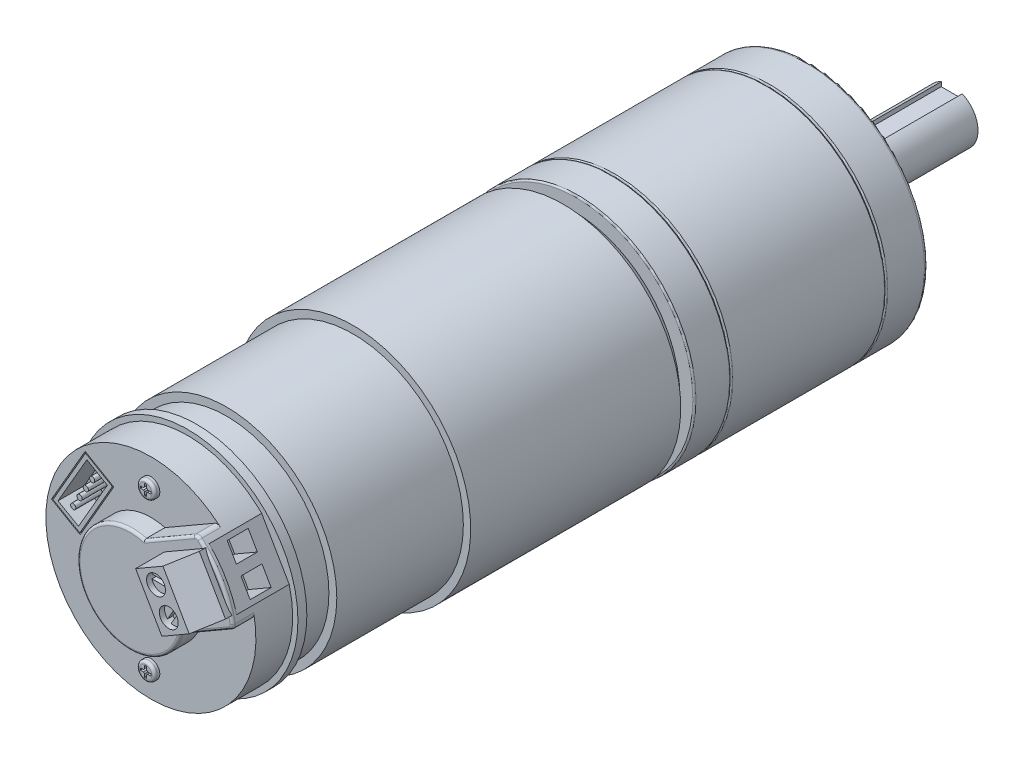
SolidWorks part; units mm, degrees
ref_plane "Front Plane" through (0, 0, 0) normal (0, 0, 1) x (1, 0, 0)
ref_plane "Top Plane" through (0, 0, 0) normal (0, 1, 0) x (1, 0, 0)
ref_plane "Right Plane" through (0, 0, 0) normal (1, 0, 0) x (0, 0, -1)
sketch "Sketch1" plane through (0, 0, 0) normal (0, 0, 1) x (1, 0, 0)
  circle A0 centre (-32.232, 14.9868) radius 22.5
extrude "Boss-Extrude1" add sketch "Sketch1" along normal blind 8
fillet "Fillet1" radius 0.3 1 edges at (-9.732, 14.9868, 8)
sketch "Sketch2" plane through (0, 0, 8) normal (0, 0, 1) x (1, 0, 0)
  circle A0 centre (-32.232, 14.9868) radius 22.5
extrude "Boss-Extrude2" add sketch "Sketch2" along normal blind 29.5
fillet "Fillet3" radius 0.3 1 edges at (-9.732, 14.9868, 37.5)
sketch "Sketch3" plane through (0, 0, 37.5) normal (0, 0, 1) x (1, 0, 0)
  circle A0 centre (-32.232, 14.9868) radius 22.5
extrude "Boss-Extrude5" add sketch "Sketch3" along normal blind 7
fillet "Fillet4" radius 0.3 3 edges at (-9.732, 14.9868, 8) (-9.732, 14.9868, 37.5) (-9.732, 14.9868, 44.5)
sketch "Sketch4" plane through (0, 0, 44.5) normal (0, 0, 1) x (1, 0, 0)
  circle A0 centre (-32.232, 14.9868) radius 5
extrude "Boss-Extrude7" add sketch "Sketch4" along normal blind 0.1
sketch "Sketch5" plane through (0, 0, 44.6) normal (0, 0, 1) x (1, 0, 0)
  circle A0 centre (-32.232, 14.9868) radius 21
extrude "Boss-Extrude8" add sketch "Sketch5" along normal blind 66.5
fillet "Fillet6" radius 2 1 edges at (-11.232, 14.9868, 44.6)
ref_plane "Plane1" through (0, 0, 47) normal (0, 0, 1) x (1, 0, 0)
sketch "Sketch6" plane through (0, 0, 47) normal (0, 0, 1) x (1, 0, 0)
  line L2 (-28.132, -5.609) -> (-28.132, -7.0347)
  line L4 (-36.332, -5.609) -> (-36.332, -7.0347)
  arc A0 (-28.132, -7.0347) -> (-36.332, -7.0347) centre (-32.232, 14.9868) ccw
  arc A1 (-28.132, -5.609) -> (-36.332, -5.609) centre (-32.232, 14.9868) ccw
  point P4 (-32.232, -6.0132)
extrude "Boss-Extrude9" add sketch "Sketch6" along normal blind 40
sketch "Sketch7" plane through (0, 0, 111.1) normal (0, 0, 1) x (1, 0, 0)
  circle A0 centre (-32.232, 14.9868) radius 19.5
extrude "Boss-Extrude10" add sketch "Sketch7" along normal blind 5.7
sketch "Sketch8" plane through (0, 0, 116.8) normal (0, 0, 1) x (1, 0, 0)
  circle A0 centre (-32.232, 14.9868) radius 21
extrude "Boss-Extrude11" add sketch "Sketch8" along normal blind 1.7
sketch "Sketch9" plane through (0, 0, 118.5) normal (0, 0, 1) x (1, 0, 0)
  circle A0 centre (-32.232, 14.9868) radius 20
extrude "Boss-Extrude12" add sketch "Sketch9" along normal blind 7
fillet "Fillet7" radius 0.7 1 edges at (-9.732, 14.9868, 0)
sketch "Sketch21" plane through (0, 0, 125.5) normal (0, 0, 1) x (1, 0, 0)
  line L0 (-45.6944, 15.3693) -> (-51.1503, 18.5193)
  line L2 (-39.2944, 26.4544) -> (-44.7503, 29.6044)
  line L3 (-44.7503, 29.6044) -> (-51.1503, 18.5193)
  line L4 (-39.2944, 26.4544) -> (-45.6944, 15.3693)
  point P6 (-42.4944, 20.9118)
extrude "Cut-Extrude5" cut sketch "Sketch21" against normal blind 5
sketch "Sketch22" plane through (0, 0, 120.5) normal (0, 0, 1) x (1, 0, 0)
  line L0 (-44.4209, 28.375) -> (-49.9209, 18.8487)
  line L1 (-49.9209, 18.8487) -> (-46.0238, 16.5987)
  line L2 (-46.0238, 16.5987) -> (-40.5238, 26.125)
  line L3 (-40.5238, 26.125) -> (-44.4209, 28.375)
  line L4 (-39.5676, 26.3812) -> (-44.6771, 29.3312)
  line L5 (-44.6771, 29.3312) -> (-50.8771, 18.5925)
  line L6 (-50.8771, 18.5925) -> (-45.7676, 15.6425)
  line L7 (-45.7676, 15.6425) -> (-39.5676, 26.3812)
  circle A0 centre (-45.8223, 21.4476) radius 0.5
  circle A1 centre (-47.0223, 19.3691) radius 0.5
  circle A2 centre (-43.4223, 25.6045) radius 0.5
  circle A3 centre (-44.6223, 23.5261) radius 0.5
extrude "Boss-Extrude20" add sketch "Sketch22" along normal blind 5 contours L6 L7 L4 L5 L3 L2 L1 L0 | A2 | A3 | A0 | A1 region at (-42.8213, 21.1006, 120.5) region at (-45.8223, 21.4476, 120.5) region at (-47.0223, 19.3691, 120.5) region at (-43.4223, 25.6045, 120.5) region at (-44.6223, 23.5261, 120.5)
sketch "Sketch23" plane through (0, 0, 125.5) normal (0, 0, 1) x (1, 0, 0)
  line L1 (-29.5473, 24.6197) -> (-20.1195, 30.0629)
  line L2 (-22.5473, 12.4954) -> (-13.1195, 17.9385)
  arc A0 (-29.5473, 24.6197) -> (-22.5473, 12.4954) centre (-32.232, 14.9868) ccw
  arc A1 (-13.1195, 17.9385) -> (-12.6399, 19.0055) centre (-13.6195, 18.8046) ccw
  arc A2 (-20.1195, 30.0629) -> (-18.9557, 29.9448) centre (-19.6195, 29.1969) cw
  arc A4 (-12.6399, 19.0055) -> (-18.9557, 29.9448) centre (-32.232, 14.9868) ccw
  point P10 (-42.4944, 20.9118)
  point P11 (-24.8334, 27.3413)
  dimension "D1" = 1
extrude "Boss-Extrude21" add sketch "Sketch23" along normal blind 4
sketch "Sketch24" plane through (0, 0, 129.5) normal (0, 0, 1) x (1, 0, 0)
  line L1 (-13.0177, 20.3067) -> (-20.6387, 15.9067)
  line L2 (-18.0177, 28.967) -> (-25.6387, 24.567)
  line L3 (-25.6387, 24.567) -> (-20.6387, 15.9067)
  line L4 (-18.0177, 28.967) -> (-13.0177, 20.3067)
  point P6 (-15.5177, 24.6368)
  point P7 (-23.1387, 20.2368)
extrude "Boss-Extrude22" add sketch "Sketch24" along normal blind 5.5
sketch "Sketch25" plane through (-12.0475, 20.8669, 0) normal (0.5, -0.866, 0) x (0.866, 0.5, 0)
  line L0 (-1.1203, 130.5) -> (-3.9203, 135)
  line L1 (-3.9203, 135) -> (-1.1203, 135)
  line L2 (-1.1203, 135) -> (-1.1203, 130.5)
extrude "Cut-Extrude6" cut sketch "Sketch25" against normal through all
sketch "Sketch26" plane through (0, 0, 125.5) normal (0, 0, 1) x (1, 0, 0)
  line L0 (-31.832, 29.7868) -> (-31.232, 29.7868)
  line L1 (-33.232, 29.7868) -> (-33.232, 30.1868)
  line L2 (-31.832, 30.1868) -> (-31.232, 30.1868)
  line L3 (-32.032, 30.3868) -> (-32.032, 30.9868)
  line L4 (-32.432, 30.3868) -> (-32.432, 30.9868)
  line L5 (-32.632, 30.1868) -> (-33.232, 30.1868)
  line L6 (-32.432, 30.9868) -> (-32.032, 30.9868)
  line L7 (-32.032, 29.5868) -> (-32.032, 28.9868)
  line L8 (-32.432, 29.5868) -> (-32.432, 28.9868)
  line L9 (-32.632, 29.7868) -> (-33.232, 29.7868)
  line L10 (-31.232, 30.1868) -> (-31.232, 29.7868)
  line L11 (-32.432, 28.9868) -> (-32.032, 28.9868)
  line L12 (-32.632, 29.7868) -> (-32.432, 29.5868)
  line L13 (-32.432, 30.3868) -> (-32.632, 30.1868)
  line L14 (-32.032, 30.3868) -> (-31.832, 30.1868)
  line L15 (-31.832, 29.7868) -> (-32.032, 29.5868)
  line L17 (-31.832, 0.1868) -> (-32.032, 0.3868)
  line L18 (-32.032, -0.4132) -> (-31.832, -0.2132)
  line L19 (-32.432, -0.4132) -> (-32.632, -0.2132)
  line L20 (-32.632, 0.1868) -> (-32.432, 0.3868)
  line L21 (-32.432, 0.9868) -> (-32.032, 0.9868)
  line L22 (-31.232, -0.2132) -> (-31.232, 0.1868)
  line L23 (-32.632, 0.1868) -> (-33.232, 0.1868)
  line L24 (-32.432, 0.3868) -> (-32.432, 0.9868)
  line L25 (-32.032, 0.3868) -> (-32.032, 0.9868)
  line L26 (-32.432, -1.0132) -> (-32.032, -1.0132)
  line L27 (-32.632, -0.2132) -> (-33.232, -0.2132)
  line L28 (-32.432, -0.4132) -> (-32.432, -1.0132)
  line L29 (-32.032, -0.4132) -> (-32.032, -1.0132)
  line L30 (-31.832, -0.2132) -> (-31.232, -0.2132)
  line L31 (-33.232, 0.1868) -> (-33.232, -0.2132)
  line L32 (-31.832, 0.1868) -> (-31.232, 0.1868)
  circle A0 centre (-32.232, 29.9868) radius 1.7
  circle A1 centre (-32.232, -0.0132) radius 1.7
  point P2 (-32.432, 29.7868)
  point P4 (-32.032, 30.1868)
  point P10 (-32.432, 30.1868)
  point P12 (-32.032, 29.7868)
  point P42 (-32.032, 0.1868)
  point P43 (-32.432, -0.2132)
  point P44 (-32.032, -0.2132)
  point P45 (-32.432, 0.1868)
  dimension "D1" = 0.2
  dimension "D2" = 0.2
  dimension "D3" = 0.2
  dimension "D4" = 0.2
  dimension "D5" = 0.2
  dimension "D6" = 0.2
  dimension "D7" = 0.2
  dimension "D8" = 0.2
extrude "Boss-Extrude23" add sketch "Sketch26" along normal blind 1
fillet "Fillet9" radius 0.5 2 edges at (-33.932, -0.0132, 126.5) (-30.532, 29.9868, 126.5)
sketch "Sketch27" plane through (0, 0, 135) normal (0, 0, 1) x (1, 0, 0)
  circle A0 centre (-21.7546, 23.8395) radius 1.8
  circle A1 centre (-19.3267, 19.6342) radius 1.8
extrude "Cut-Extrude7" cut sketch "Sketch27" against normal blind 1
sketch "Sketch29" plane through (0, 0, 134) normal (0, 0, 1) x (1, 0, 0)
  line L1 (-23.5096, 23.4395) -> (-19.9996, 23.4395)
  line L3 (-23.5096, 24.2395) -> (-19.9996, 24.2395)
  line L7 (-19.8577, 17.9143) -> (-18.1028, 20.9541)
  line L8 (-20.5506, 18.3143) -> (-18.7956, 21.3541)
  arc A0 (-23.5096, 24.2395) -> (-23.5096, 23.4395) centre (-21.7546, 23.8395) ccw
  arc A1 (-19.9996, 23.4395) -> (-19.9996, 24.2395) centre (-21.7546, 23.8395) ccw
  arc A2 (-18.6805, 21.3142) -> (-18.1028, 20.9541) centre (-19.3267, 19.6342) cw
  arc A3 (-19.8577, 17.9143) -> (-20.5506, 18.3143) centre (-19.3267, 19.6342) cw
  arc A4 (-18.7956, 21.3541) -> (-18.1028, 20.9541) centre (-19.3267, 19.6342) cw
  circle M1 centre (-21.7546, 23.8395) radius 1.8
extrude "Cut-Extrude8" cut sketch "Sketch29" against normal blind 1 contours L3 L1 M1 | A4 L8 A3 L7 A2 region at (-21.7546, 23.8395, 134) region at (-19.3267, 19.6342, 134)
sketch "Sketch30" plane through (-0.9702, -0.5601, 0) normal (0.866, 0.5, 0) x (0, 0, -1)
  line L5 (-118.5, 23.595) -> (-128.5, 23.595)
  line L6 (-118.5, 23.595) -> (-118.5, 34.595)
  line L7 (-118.5, 34.595) -> (-128.5, 34.595)
  line L8 (-128.5, 23.595) -> (-128.5, 34.595)
  point P4 (-123.5, 29.095)
extrude "Cut-Extrude9" cut sketch "Sketch30" along normal blind 1
sketch "Sketch31" plane through (-0.9702, -0.5601, 0) normal (0.866, 0.5, 0) x (0, 0, -1)
  line L6 (-125.5, 28.2225) -> (-121.5, 28.2225)
  line L7 (-125.5, 29.9675) -> (-121.5, 29.9675)
  line L8 (-125.5, 29.9675) -> (-125.5, 33.4675)
  line L9 (-125.5, 33.4675) -> (-121.5, 33.4675)
  line L10 (-121.5, 29.9675) -> (-121.5, 33.4675)
  line L13 (-121.5, 28.2225) -> (-121.5, 24.7225)
  line L14 (-125.5, 24.7225) -> (-121.5, 24.7225)
  line L15 (-125.5, 28.2225) -> (-125.5, 24.7225)
  point P9 (-123.5, 31.7175)
extrude "Cut-Extrude10" cut sketch "Sketch31" against normal blind 5
fillet "Fillet10" radius 0.5 6 edges at (-17.8334, 15.217, 129.5) (-12.7074, 18.3946, 129.5) (-14.9115, 24.9868, 129.5) (-19.5185, 30.1918, 129.5) (-24.8334, 27.3413, 129.5) (-40.8922, 9.9868, 129.5)
sketch "Sketch32" plane through (0, 0, 0) normal (0, 0, -1) x (-1, 0, 0)
  circle A0 centre (32.232, 14.9868) radius 13
extrude "Boss-Extrude24" add sketch "Sketch32" along normal blind 1.5
sketch "Sketch33" plane through (0, 0, 0) normal (0, 0, -1) x (-1, 0, 0)
  circle A1 centre (32.232, 32.7368) radius 3.85
  circle A2 centre (49.982, 14.9868) radius 3.85
  circle A3 centre (32.232, -2.7632) radius 3.85
  circle A4 centre (14.482, 14.9868) radius 3.85
  point P14 (32.232, 14.9868)
  dimension "D1" = 4
extrude "Cut-Extrude11" cut sketch "Sketch33" against normal blind 3
sketch "Sketch34" plane through (0, 0, 3) normal (0, 0, -1) x (-1, 0, 0)
  line L1 (32.232, 35.0462) -> (30.232, 33.8915)
  line L2 (30.232, 33.8915) -> (30.232, 31.5821)
  line L3 (30.232, 31.5821) -> (32.232, 30.4274)
  line L4 (32.232, 30.4274) -> (34.232, 31.5821)
  line L5 (34.232, 31.5821) -> (34.232, 33.8915)
  line L6 (34.232, 33.8915) -> (32.232, 35.0462)
  line L7 (52.2914, 14.9868) -> (51.1367, 16.9868)
  line L8 (51.1367, 12.9868) -> (52.2914, 14.9868)
  line L9 (48.8273, 12.9868) -> (51.1367, 12.9868)
  line L10 (47.6726, 14.9868) -> (48.8273, 12.9868)
  line L11 (48.8273, 16.9868) -> (47.6726, 14.9868)
  line L12 (51.1367, 16.9868) -> (48.8273, 16.9868)
  line L13 (32.232, -5.0726) -> (34.232, -3.9179)
  line L14 (30.232, -3.9179) -> (32.232, -5.0726)
  line L15 (30.232, -1.6085) -> (30.232, -3.9179)
  line L16 (32.232, -0.4538) -> (30.232, -1.6085)
  line L17 (34.232, -1.6085) -> (32.232, -0.4538)
  line L18 (34.232, -3.9179) -> (34.232, -1.6085)
  line L19 (12.1726, 14.9868) -> (13.3273, 12.9868)
  line L20 (13.3273, 16.9868) -> (12.1726, 14.9868)
  line L21 (15.6367, 16.9868) -> (13.3273, 16.9868)
  line L22 (16.7914, 14.9868) -> (15.6367, 16.9868)
  line L23 (15.6367, 12.9868) -> (16.7914, 14.9868)
  line L24 (13.3273, 12.9868) -> (15.6367, 12.9868)
  circle A0 centre (32.232, 32.7368) radius 3
  circle A1 centre (32.232, 32.7368) radius 2 construction
  circle A2 centre (49.982, 14.9868) radius 3
  circle A3 centre (32.232, -2.7632) radius 3
  circle A4 centre (14.482, 14.9868) radius 3
  point P40 (32.232, 14.9868)
  dimension "D1" = 4
extrude "Boss-Extrude25" add sketch "Sketch34" along normal blind 3
fillet "Fillet11" radius 0.5 24 edges at (-30.232, -2.7632, 3) (-31.232, -1.0311, 3) (-33.232, -1.0311, 3) (-34.232, -2.7632, 3) (-33.232, -4.4952, 3) (-31.232, -4.4952, 3) (-49.982, 12.9868, 3) (-48.2499, 13.9868, 3) (-48.2499, 15.9868, 3) (-49.982, 16.9868, 3) (-51.714, 15.9868, 3) (-51.714, 13.9868, 3) (-14.482, 16.9868, 3) (-16.214, 15.9868, 3) (-16.214, 13.9868, 3) (-14.482, 12.9868, 3) (-12.7499, 13.9868, 3) (-12.7499, 15.9868, 3) (-34.232, 32.7368, 3) (-33.232, 31.0048, 3) (-31.232, 31.0048, 3) (-30.232, 32.7368, 3) (-31.232, 34.4689, 3) (-33.232, 34.4689, 3)
sketch "Sketch35" plane through (0, 0, 0) normal (0, 0, -1) x (-1, 0, 0)
  circle A2 centre (44.7831, 27.538) radius 2
  circle A4 centre (44.7831, 2.4357) radius 2
  circle A6 centre (19.6808, 2.4357) radius 2
  circle A8 centre (19.6808, 27.538) radius 2
  point P22 (32.232, 14.9868)
  dimension "D1" = 17.75
  dimension "D2" = 4
extrude "Cut-Extrude12" cut sketch "Sketch35" against normal blind 5
sketch "Sketch36" plane through (0, 0, -1.5) normal (0, 0, -1) x (-1, 0, 0)
  circle A0 centre (32.232, 14.9868) radius 5
  dimension "D1" = 10
extrude "Boss-Extrude26" add sketch "Sketch36" along normal blind 25.5
sketch "Sketch37" plane through (0, 0, -27) normal (0, 0, -1) x (-1, 0, 0)
  line L1 (30.232, 21.2368) -> (34.232, 21.2368)
  line L2 (30.232, 21.2368) -> (30.232, 18.7368)
  line L3 (30.232, 18.7368) -> (34.232, 18.7368)
  line L4 (34.232, 21.2368) -> (34.232, 18.7368)
  line L5 (30.232, 21.2368) -> (34.232, 18.7368) construction
  line L6 (30.232, 18.7368) -> (34.232, 21.2368) construction
  circle A0 centre (32.232, 14.9868) radius 5 construction
  circle A1 centre (32.232, 14.9868) radius 5 construction
  point P0 (32.232, 19.9868)
  dimension "D1" = 4
  dimension "D2" = 2.5
extrude "Cut-Extrude13" cut sketch "Sketch37" against normal blind 20
fillet "Fillet12" radius 2 2 edges at (-30.232, 19.1531, -7) (-34.232, 19.1531, -7)
